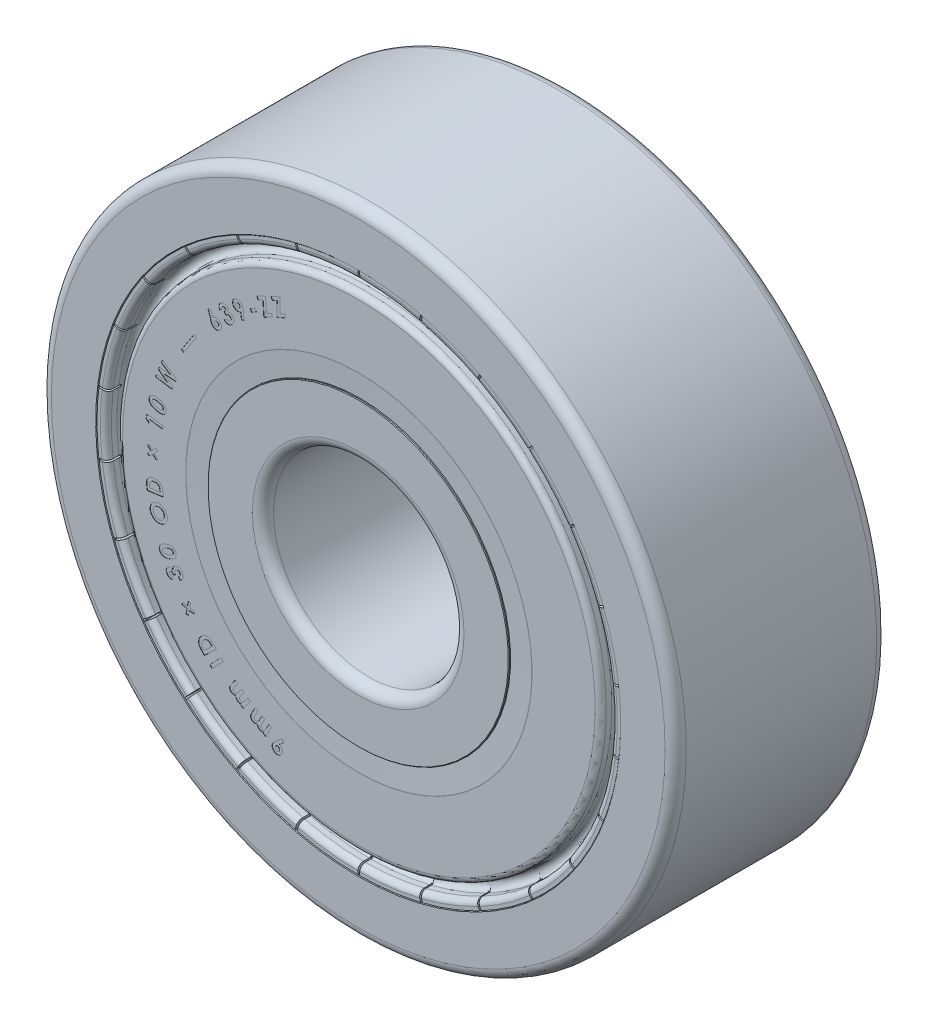
SolidWorks part; units mm, degrees
material "AISI 316 Annealed Stainless Steel Bar (SS)"
ref_plane "Front" through (0, 0, 0) normal (0, 0, 1) x (1, 0, 0)
ref_plane "Top" through (0, 0, 0) normal (0, 1, 0) x (1, 0, 0)
ref_plane "Right" through (0, 0, 0) normal (1, 0, 0) x (0, 0, -1)
sketch "LAYOUT R" plane through (0, 0, 0) normal (1, 0, 0) x (0, 0, -1)
  line L0 (-4.5, 4.5) -> (4.5, 4.5)
  line L1 (5, -15) -> (-5, -15) construction
  line L2 (5, -15) -> (5, 2.5781) construction
  line L3 (4.5, 15) -> (-4.5, 15)
  line L4 (-5, -15) -> (-5, 14.5) construction
  line L6 (2.6982, 0) -> (-2.6982, 0) construction
  line L7 (-4.97, 7.125) -> (4.97, 7.125)
  line L8 (-4.97, 12.375) -> (4.97, 12.375)
  line L11 (-8.89, 0) -> (8.89, 0) construction
  line L12 (-5, 14.5) -> (-5, 12.405)
  line L13 (5, 14.5) -> (5, 12.405)
  line L16 (-5, 7.095) -> (-5, 5)
  line L17 (5, 7.095) -> (5, 5)
  line L30 (-4.97, 12.375) -> (-4.97, 7.125) construction
  line L31 (4.97, 12.375) -> (4.97, 7.125) construction
  line L32 (-4.97, 8.175) -> (4.97, 8.175) construction
  line L33 (-4.9698, 8.175) -> (-4.9239, 7.125)
  line L34 (4.9698, 8.175) -> (4.9239, 7.125)
  line L35 (-4.97, 11.955) -> (4.97, 11.955) construction
  line L38 (-5, 12.405) -> (5, 12.405) construction
  line L39 (-4.97, 12.375) -> (-4.97, 12.2175)
  line L40 (-4.7075, 11.955) -> (-4.445, 11.955)
  line L41 (-4.97, 8.1865) -> (-4.97, 11.1675)
  line L42 (-4.7075, 11.43) -> (-4.445, 11.43)
  line L43 (4.97, 8.1865) -> (4.97, 11.1675)
  line L44 (4.7075, 11.43) -> (4.445, 11.43)
  line L45 (4.7075, 11.955) -> (4.445, 11.955)
  line L46 (-4.97, 11.43) -> (4.97, 11.43) construction
  line L50 (-1.3199, 11.325) -> (1.3199, 11.325) construction
  line L53 (4.97, 7.125) -> (5, 7.095)
  line L54 (-4.97, 7.125) -> (-5, 7.095)
  line L56 (-5, 7.095) -> (5, 7.095) construction
  line L57 (5, 12.405) -> (4.97, 12.375) construction
  line L58 (5, 12.405) -> (4.97, 12.375)
  line L60 (-5, 12.405) -> (-4.97, 12.375) construction
  line L61 (-5, 12.405) -> (-4.97, 12.375)
  line L64 (-4.445, 11.43) -> (-4.445, 11.955) construction
  line L65 (4.445, 11.43) -> (4.445, 11.955) construction
  line L66 (4.97, 12.375) -> (4.97, 12.2175)
  arc A2 (-4.7075, 11.43) -> (-4.97, 11.1675) centre (-4.7075, 11.1675) ccw
  arc A3 (4.97, 11.1675) -> (4.7075, 11.43) centre (4.7075, 11.1675) ccw
  arc A4 (4.9698, 8.175) -> (4.97, 8.1865) centre (4.7075, 8.1865) ccw
  arc A5 (-4.97, 8.1865) -> (-4.9698, 8.175) centre (-4.7075, 8.1865) ccw
  arc A6 (-4.445, 11.43) -> (-4.445, 11.955) centre (-4.445, 11.6925) ccw
  arc A7 (4.445, 11.955) -> (4.445, 11.43) centre (4.445, 11.6925) ccw
  arc A8 (-4.5, 15) -> (-5, 14.5) centre (-4.5, 14.5) ccw
  arc A9 (-5, 5) -> (-4.5, 4.5) centre (-4.5, 5) ccw
  arc A10 (4.5, 4.5) -> (5, 5) centre (4.5, 5) ccw
  arc A11 (-4.97, 12.2175) -> (-4.7075, 11.955) centre (-4.7075, 12.2175) ccw
  arc A12 (4.7075, 11.955) -> (4.97, 12.2175) centre (4.7075, 12.2175) ccw
  arc A13 (5, 14.5) -> (4.5, 15) centre (4.5, 14.5) ccw
  point P0 (0, 0)
  point P7 (-4.5, 15)
  point P8 (-4.7075, 11.955)
  point P15 (0, 0)
  point P29 (-4.97, 12.2175)
  point P38 (-4.9698, 8.175)
  point P54 (-4.97, 11.1675)
  point P55 (-4.7075, 11.43)
  point P56 (-4.97, 11.1675)
  point P58 (-4.97, 8.1865)
  point P59 (-4.9698, 8.175)
  point P60 (4.7075, 11.43)
  point P62 (4.97, 11.1675)
  point P63 (4.97, 8.1865)
  point P64 (4.9698, 8.175)
  point P71 (-5, 14.5)
  point P72 (-5, 5)
  point P73 (-4.5, 4.5)
  point P74 (4.5, 4.5)
  point P75 (5, 5)
  point P80 (4.5, 15)
  point P81 (4.7075, 11.955)
  point P88 (4.97, 12.2175)
  point P91 (5, 14.5)
  dimension "D21" = 0.525
  dimension "D33" = 0.5
  dimension "D3" = 4.5
  dimension "D4" = 7.125
  dimension "D5" = 12.375
  dimension "D24" = 10
  dimension "D6" = 9.97
  dimension "D7" = 9.97
  dimension "D11" = 1.05
  dimension "D12" = 2.5
  dimension "D13" = 2.5
  dimension "D14" = 0.42
  dimension "D17" = 0.03
  dimension "D18" = 0.525
  dimension "D19" = 0.525
  dimension "D20" = 0.525
  dimension "D15" = 1.05
  dimension "D23" = 45
  dimension "D25" = 45
  dimension "D27" = 0.03
  dimension "D28" = 15
  dimension "D29" = 10
  dimension "D30" = 30
  dimension "D8" = 5
  dimension "D31" = 45
  dimension "D32" = 45
sketch "Sketch R, INNER BODY" plane through (0, 0, 0) normal (1, 0, 0) x (0, 0, -1)
  line L1 (-4.97, 7.125) -> (-5, 7.095) construction
  line L3 (-5, 7.095) -> (-5, 5) construction
  line L12 (-8.89, 0) -> (8.89, 0) construction
  line L13 (-8.89, 0) -> (8.89, 0) construction
  line L14 (-4.5, 4.5) -> (4.5, 4.5) construction
  line L15 (5, 7.095) -> (5, 5) construction
  line L16 (4.97, 7.125) -> (5, 7.095) construction
  line L17 (-4.97, 7.125) -> (4.97, 7.125) construction
  line L18 (-4.97, 7.125) -> (-5, 7.095)
  line L19 (-5, 7.095) -> (-5, 5)
  line L20 (-4.5, 4.5) -> (4.5, 4.5)
  line L21 (5, 7.095) -> (5, 5)
  line L22 (4.97, 7.125) -> (5, 7.095)
  line L23 (-4.97, 7.125) -> (4.97, 7.125)
  arc A0 (-5, 5) -> (-4.5, 4.5) centre (-4.5, 5) ccw construction
  arc A1 (4.5, 4.5) -> (5, 5) centre (4.5, 5) ccw construction
  arc A2 (-5, 5) -> (-4.5, 4.5) centre (-4.5, 5) ccw
  arc A3 (4.5, 4.5) -> (5, 5) centre (4.5, 5) ccw
sketch "Sketch R, OUTER BODY" plane through (0, 0, 0) normal (1, 0, 0) x (0, 0, -1)
  line L8 (-8.89, 0) -> (8.89, 0) construction
  line L9 (-8.89, 0) -> (8.89, 0) construction
  line L31 (-5, 14.5) -> (-5, 12.405) construction
  line L84 (-5, 12.405) -> (-4.97, 12.375) construction
  line L85 (-4.97, 12.375) -> (4.97, 12.375) construction
  line L86 (5, 12.405) -> (4.97, 12.375) construction
  line L87 (5, 14.5) -> (5, 12.405) construction
  line L88 (4.5, 15) -> (-4.5, 15) construction
  line L89 (-5, 14.5) -> (-5, 12.405)
  line L90 (-5, 12.405) -> (-4.97, 12.375)
  line L91 (-4.97, 12.375) -> (4.97, 12.375)
  line L92 (5, 12.405) -> (4.97, 12.375)
  line L93 (5, 14.5) -> (5, 12.405)
  line L94 (4.5, 15) -> (-4.5, 15)
  arc A6 (5, 14.5) -> (4.5, 15) centre (4.5, 14.5) ccw construction
  arc A7 (-4.5, 15) -> (-5, 14.5) centre (-4.5, 14.5) ccw construction
  arc A8 (5, 14.5) -> (4.5, 15) centre (4.5, 14.5) ccw
  arc A9 (-4.5, 15) -> (-5, 14.5) centre (-4.5, 14.5) ccw
sketch "Sketch R, SHIELD FACES" plane through (0, 0, 0) normal (1, 0, 0) x (0, 0, -1)
  line L0 (-8.89, 0) -> (8.89, 0) construction
  line L1 (-8.89, 0) -> (8.89, 0) construction
  line L29 (-4.97, 12.375) -> (-4.97, 12.2175) construction
  line L32 (-4.7075, 11.955) -> (-4.445, 11.955) construction
  line L34 (-4.7075, 11.43) -> (-4.445, 11.43) construction
  line L36 (-4.97, 8.1865) -> (-4.97, 11.1675) construction
  line L38 (-4.9698, 8.175) -> (-4.9239, 7.125) construction
  line L39 (-4.97, 7.125) -> (4.97, 7.125) construction
  line L40 (4.9698, 8.175) -> (4.9239, 7.125) construction
  line L43 (4.97, 8.1865) -> (4.97, 11.1675) construction
  line L79 (4.7075, 11.43) -> (4.445, 11.43) construction
  line L80 (4.7075, 11.955) -> (4.445, 11.955) construction
  line L81 (4.97, 12.375) -> (4.97, 12.2175) construction
  line L82 (-4.97, 12.375) -> (4.97, 12.375) construction
  line L83 (-4.97, 12.375) -> (-4.97, 12.2175)
  line L84 (-4.7075, 11.955) -> (-4.445, 11.955)
  line L85 (-4.7075, 11.43) -> (-4.445, 11.43)
  line L86 (-4.97, 8.1865) -> (-4.97, 11.1675)
  line L87 (-4.9698, 8.175) -> (-4.9239, 7.125)
  line L88 (-4.9239, 7.125) -> (4.9239, 7.125)
  line L89 (4.9698, 8.175) -> (4.9239, 7.125)
  line L90 (4.97, 8.1865) -> (4.97, 11.1675)
  line L91 (4.7075, 11.43) -> (4.445, 11.43)
  line L92 (4.7075, 11.955) -> (4.445, 11.955)
  line L93 (4.97, 12.375) -> (4.97, 12.2175)
  line L94 (-4.97, 12.375) -> (4.97, 12.375)
  arc A28 (-4.97, 12.2175) -> (-4.7075, 11.955) centre (-4.7075, 12.2175) ccw construction
  arc A29 (-4.445, 11.43) -> (-4.445, 11.955) centre (-4.445, 11.6925) ccw construction
  arc A30 (-4.7075, 11.43) -> (-4.97, 11.1675) centre (-4.7075, 11.1675) ccw construction
  arc A31 (4.97, 11.1675) -> (4.7075, 11.43) centre (4.7075, 11.1675) ccw construction
  arc A32 (4.445, 11.955) -> (4.445, 11.43) centre (4.445, 11.6925) ccw construction
  arc A33 (4.7075, 11.955) -> (4.97, 12.2175) centre (4.7075, 12.2175) ccw construction
  arc A34 (-4.97, 12.2175) -> (-4.7075, 11.955) centre (-4.7075, 12.2175) ccw
  arc A35 (-4.445, 11.43) -> (-4.445, 11.955) centre (-4.445, 11.6925) ccw
  arc A36 (-4.7075, 11.43) -> (-4.97, 11.1675) centre (-4.7075, 11.1675) ccw
  arc A37 (4.97, 11.1675) -> (4.7075, 11.43) centre (4.7075, 11.1675) ccw
  arc A38 (4.445, 11.955) -> (4.445, 11.43) centre (4.445, 11.6925) ccw
  arc A39 (4.7075, 11.955) -> (4.97, 12.2175) centre (4.7075, 12.2175) ccw
  arc A40 (-4.97, 8.1865) -> (-4.9698, 8.175) centre (-4.7075, 8.1865) ccw construction
  arc A41 (-4.97, 8.1865) -> (-4.9698, 8.175) centre (-4.7075, 8.1865) ccw
  arc A42 (4.9698, 8.175) -> (4.97, 8.1865) centre (4.7075, 8.1865) ccw construction
  arc A43 (4.9698, 8.175) -> (4.97, 8.1865) centre (4.7075, 8.1865) ccw
revolve "Revolve INNER BODY" add sketch "Sketch R, INNER BODY" angle 360 about L13
revolve "Revolve OUTER BODY" add sketch "Sketch R, OUTER BODY" angle 360 about L9
revolve "Revolve SHIELDS" add sketch "Sketch R, SHIELD FACES" angle 360 about L1
sketch "Sketch TEXT RADIUS 1 — MANUALLY ASSIGN TEXT AND FONT SIZE (FROM EQUATIONS)" plane through (0, 0, 4.97) normal (0, 0, 1) x (1, 0, 0)
  circle A0 centre (0, 0) radius 9.36 construction
  text T0 "<b>9mm ID × 30 OD × 10 W  —  639-ZZ</b>" font "Century Gothic" height 0.78
  dimension "D1" = 18.72
extrude "Cut-Extrude LABEL 1" cut sketch "Sketch TEXT RADIUS 1 — MANUALLY ASSIGN TEXT AND FONT SIZE (FROM EQUATIONS)" against normal blind 0.0127
sketch "Sketch TEXT RADIUS 2 — MANUALLY ASSIGN TEXT AND FONT SIZE (FROM EQUATIONS)" plane through (0, 0, -4.97) normal (0, 0, -1) x (-1, 0, 0)
  circle A0 centre (0, 0) radius 9.36 construction
  text T0 "<b>9mm ID × 30 OD × 10 W  —  639-ZZ</b>" font "Century Gothic" height 0.78
  dimension "D1" = 18.72
extrude "Cut-Extrude LABEL 2" cut sketch "Sketch TEXT RADIUS 2 — MANUALLY ASSIGN TEXT AND FONT SIZE (FROM EQUATIONS)" against normal blind 0.0127
sketch "LAYOUT F, SLIT SEED" plane through (0, 0, 0) normal (0, 0, 1) x (1, 0, 0)
  line L0 (0, 0) -> (0, 12.7) construction
  line L3 (0.042, 12.3749) -> (0.042, 11.897)
  line L4 (-0.042, 12.3749) -> (-0.042, 11.897)
  circle A4 centre (0, 0) radius 11.85
  circle A5 centre (0, 0) radius 12.375
  circle A6 centre (0, 11.85) radius 0.063
  point P13 (-0.042, 12.3749)
  point P15 (0.042, 12.3749)
  dimension "D1" = 24.75
  dimension "D2" = 23.7
  dimension "D3" = 0.126
  dimension "D4" = 0.042
  dimension "D5" = 0.042
sketch "Sketch F, SLIT SEED" plane through (0, 0, 4.97) normal (0, 0, 1) x (1, 0, 0)
  line L1 (0.042, 12.3749) -> (0.042, 11.897) construction
  line L8 (-0.042, 12.3749) -> (-0.042, 11.897) construction
  line L9 (0.042, 12.3749) -> (0.042, 11.897)
  line L10 (-0.042, 12.3749) -> (-0.042, 11.897)
  circle A1 centre (0, 11.85) radius 0.063 construction
  circle A8 centre (0, 0) radius 12.375 construction
  arc A9 (-0.042, 11.897) -> (0.042, 11.897) centre (0, 11.85) ccw
  arc A10 (0.042, 12.3749) -> (-0.042, 12.3749) centre (0, 0) ccw
extrude "Cut-Extrude SLIT SEED F" cut sketch "Sketch F, SLIT SEED" along normal blind 0.635 from surface starting at face at (9.1339, 3.5193, -4.97)
extrude "Cut-Extrude SLIT SEED B" cut sketch "Sketch F, SLIT SEED<2>" against normal blind 0.635
sketch "Sketch F, SLIT SEED<2>" plane through (0, 0, 4.97) normal (0, 0, 1) x (1, 0, 0) same geometry as "Sketch F, SLIT SEED"
pattern_circular "CirPattern1" count 26 over 360 of "Cut-Extrude SLIT SEED F"
pattern_circular "CirPattern2" count 26 over 360 of "Cut-Extrude SLIT SEED B" reverse direction yes
equation "\"_i__BORE\" = 9"
equation "\"_i__OUTSIDE_DIAMETER\" = 30"
equation "\"_i__WIDTH\"= 10"
equation "\"_user_applied_FONT_SIZE\"= int ( \"BODY_SPAN__SHIELD__OF_RADIUS\" * \"g_param__FONT_SIZE_RATIO\" * 100 ) / 100'MANUALLY ASSIGN TO FONT"
equation "\"BODY__HALF_WIDTH\"= \"_i__WIDTH\" / 2"
equation "\"BODY_SPAN___OF_DIAMETER\"= \"_i__OUTSIDE_DIAMETER\" - \"_i__BORE\""
equation "\"BODY_SPAN___OF_RADIUS\"= \"BODY_SPAN___OF_DIAMETER\" / 2"
equation "\"BODY_SPAN__BORE_AND_OD__OF RADIUS\"= ( \"BODY_SPAN___OF_RADIUS\" - \"BODY_SPAN__SHIELD__OF_RADIUS\" ) / 2"
equation "\"BODY_SPAN__SHIELD__OF_RADIUS\"= \"BODY_SPAN___OF_RADIUS\" * \"g_param__SHIELD_PANEL_SPAN__RATIO_OF_BODY_RADIAN\""
equation "\"BORE__RADIUS\"= \"_i__BORE\" / 2"
equation "\"CORNER_RADII\"= \"_i__WIDTH\" * \"g_param__CORNER_RADII__RATIO_TO_WIDTH\""
equation "\"OUTSIDE_RADIUS\"= \"_i__OUTSIDE_DIAMETER\" / 2"
equation "\"RING_INNER__OUTSIDE_RADIUS\"= \"BORE__RADIUS\" + \"BODY_SPAN__BORE_AND_OD__OF RADIUS\""
equation "\"RING_OUTER__INSIDE_DIAMETER\"= \"RING_OUTER__INSIDE_RADIUS\" * 2"
equation "\"RING_OUTER__INSIDE_RADIUS\"= ( \"_i__OUTSIDE_DIAMETER\" / 2 ) - \"BODY_SPAN__BORE_AND_OD__OF RADIUS\""
equation "\"SHIELD__BOTTOM_AND_TOP_REGIONS_SPAN\"= \"BODY_SPAN__SHIELD__OF_RADIUS\" * \"g_param__SHIELD__TOP_AND_BOTTOM_REGIONS_RATIO\""
equation "\"SHIELD__COMPRESSION_FILLET_DIAMETER\"= \"BODY_SPAN__SHIELD__OF_RADIUS\" * \"g_param__SHIELD_COMPRESSION_FILLET_DIAMETER_RATIO\""
equation "\"SHIELD__COMPRESSION_FILLET_RADIUS\"= \"SHIELD__COMPRESSION_FILLET_DIAMETER\" / 2"
equation "\"SHIELD__FACE_FILLET_DIAMETER\"= \"BODY_SPAN__SHIELD__OF_RADIUS\" * \"g_param__SHIELD_FACE_FILLET_RATIO\""
equation "\"SHIELD__FACE_INSET\"= \"SIDE_FACE_CHAMFERS\""
equation "\"SHIELD__FACE_TO_OPPOSING_BRG_BODY_FACE\"= \"_i__WIDTH\" - \"SHIELD__FACE_INSET\""
equation "\"SHIELD__HALF_SLIT_WIDTH\"= \"SHIELD__SLIT_WIDTH\" / 2"
equation "\"SHIELD__HALF_WALL\"= \"SHIELD__WALL\" / 2"
equation "\"SHIELD__SLIT_WIDTH\"= \"SHIELD__WALL\" / 5"
equation "\"SHIELD__WALL\"= \"BODY_SPAN__SHIELD__OF_RADIUS\" * \"g_param__SHIELD_WALL_TO_SPAN_RATIO\""
equation "\"SHIELD_SLIT__INSIDE_TERMINUS__DIAMETER\"= \"RING_OUTER__INSIDE_DIAMETER\" - \"SHIELD__BOTTOM_AND_TOP_REGIONS_SPAN\""
equation "\"SHIELD_SLIT__KEYHOLE_DIAMETER\"= \"SHIELD__SLIT_WIDTH\" * 1.5"
equation "\"SIDE_FACE_CHAMFERS\"= \"_i__OUTSIDE_DIAMETER\" * \"g_param__SIDE_CHAMFERS__RATIO_TO_OD\""
equation "\"TEXT_RADIUS\"= \"_i__BORE\" + ( \"BODY_SPAN___OF_DIAMETER\" / 2 ) - \"_user_applied_FONT_SIZE\""
equation "\"WIDTH__HALF\"= \"_i__WIDTH\" / 2"
equation "\"D1@CirPattern1\" = \"g_param__SHIELD__NUMBER_OF_SLITS\""
equation "\"D1@CirPattern2\" = \"g_param__SHIELD__NUMBER_OF_SLITS\""
equation "\"D1@LAYOUT F, SLIT SEED\"=\"RING_OUTER__INSIDE_DIAMETER\""
equation "\"D1@Sketch TEXT RADIUS 1 — MANUALLY ASSIGN TEXT AND FONT SIZE (FROM EQUATIONS)\" = \"TEXT_RADIUS\""
equation "\"D1@Sketch TEXT RADIUS 2 — MANUALLY ASSIGN TEXT AND FONT SIZE (FROM EQUATIONS)\" = \"TEXT_RADIUS\""
equation "\"D11@LAYOUT R\"=\"SHIELD__BOTTOM_AND_TOP_REGIONS_SPAN\""
equation "\"D12@LAYOUT R\" = \"g_param__SHIELD__INSIDE_BEVEL_ANGLE__DEGREES\""
equation "\"D13@LAYOUT R\"= \"g_param__SHIELD__INSIDE_BEVEL_ANGLE__DEGREES\""
equation "\"D14@LAYOUT R\"=\"SHIELD__WALL\""
equation "\"D15@LAYOUT R\"=\"SHIELD__BOTTOM_AND_TOP_REGIONS_SPAN\""
equation "\"D17@LAYOUT R\"=\"SIDE_FACE_CHAMFERS\""
equation "\"D18@LAYOUT R\"=\"SHIELD__COMPRESSION_FILLET_DIAMETER\""
equation "\"D19@LAYOUT R\"=\"SHIELD__COMPRESSION_FILLET_DIAMETER\""
equation "\"D2@LAYOUT F, SLIT SEED\"=\"SHIELD_SLIT__INSIDE_TERMINUS__DIAMETER\""
equation "\"D20@LAYOUT R\"=\"SHIELD__COMPRESSION_FILLET_DIAMETER\""
equation "\"D21@LAYOUT R\"=\"SHIELD__FACE_FILLET_DIAMETER\""
equation "\"D24@LAYOUT R\"=\"_i__WIDTH\""
equation "\"D27@LAYOUT R\"=\"SIDE_FACE_CHAMFERS\""
equation "\"D28@LAYOUT R\"=\"OUTSIDE_RADIUS\""
equation "\"D3@LAYOUT F, SLIT SEED\"=\"SHIELD_SLIT__KEYHOLE_DIAMETER\""
equation "\"D3@LAYOUT R\"=\"BORE__RADIUS\""
equation "\"D30@LAYOUT R\"=\"_i__OUTSIDE_DIAMETER\""
equation "\"D33@LAYOUT R\"=\"CORNER_RADII\""
equation "\"D4@LAYOUT F, SLIT SEED\"=\"SHIELD__HALF_SLIT_WIDTH\""
equation "\"D4@LAYOUT R\"=\"RING_INNER__OUTSIDE_RADIUS\""
equation "\"D5@LAYOUT F, SLIT SEED\"=\"SHIELD__HALF_SLIT_WIDTH\""
equation "\"D5@LAYOUT R\"=\"RING_OUTER__INSIDE_RADIUS\""
equation "\"D6@LAYOUT R\"=\"SHIELD__FACE_TO_OPPOSING_BRG_BODY_FACE\""
equation "\"D7@LAYOUT R\"=\"SHIELD__FACE_TO_OPPOSING_BRG_BODY_FACE\""
equation "\"D8@LAYOUT R\"=\"WIDTH__HALF\""
equation "\"g_param__CORNER_RADII__RATIO_TO_WIDTH\"= 0.05'ISO MAX IS 0.07 WHERE WIDTH IS LESS THAN DIAMETER"
equation "\"g_param__FONT_SIZE_RATIO\"= 0.15'EXPRESSES RADIAL PROPORTION OF SHIELD FACE"
equation "\"g_param__INDICIA__EXTRUSION_DEPTH\"=0.013'CONCAVE-EMBOSSED INDICIA ON SHIELD FACES"
equation "\"g_param__SHIELD__INSIDE_BEVEL_ANGLE__DEGREES\"= 2.5'SHOULD BE GREATER THAN 0 AND LESS THAN OR EQUAL TO 10, ORIGINALLY 1"
equation "\"g_param__SHIELD__NUMBER_OF_SLITS\"=26'OPTIONAL NUMBER OF SHIELD COMPRESSION RING SLITS"
equation "\"g_param__SHIELD__TOP_AND_BOTTOM_REGIONS_RATIO\"=0.2'PART OF RADIAL SHIELD SPAN OCCUPIED BY INMOST BEVEL, ORIGINALLY 0.2"
equation "\"g_param__SHIELD_COMPRESSION_FILLET_DIAMETER_RATIO\"=0.1'ORIGINALLY 0,1"
equation "\"g_param__SHIELD_FACE_FILLET_RATIO\"=0.1'ORIGINALLY 0.1"
equation "\"g_param__SHIELD_FACE_INSET__RATIO_OF_WIDTH\"= 0.035'ISO-UNSPECIFIED, SHOULD BE AT LEAST 0.025 and LESS THAN 0.036"
equation "\"g_param__SHIELD_PANEL_SPAN__RATIO_OF_BODY_RADIAN\"= 0.5'ISO-UNSPECIFIED, ORIGINALLY 0.5"
equation "\"g_param__SHIELD_WALL_TO_SPAN_RATIO\"=0.08'SHOULD BE LESS THAN 0.015, ORIGINALLY 0.08, PRESCRIBES MATERIAL THICKNESS"
equation "\"g_param__SIDE_CHAMFERS__RATIO_TO_OD\"= 0.001'NOT ISO-SPECIFIED"
